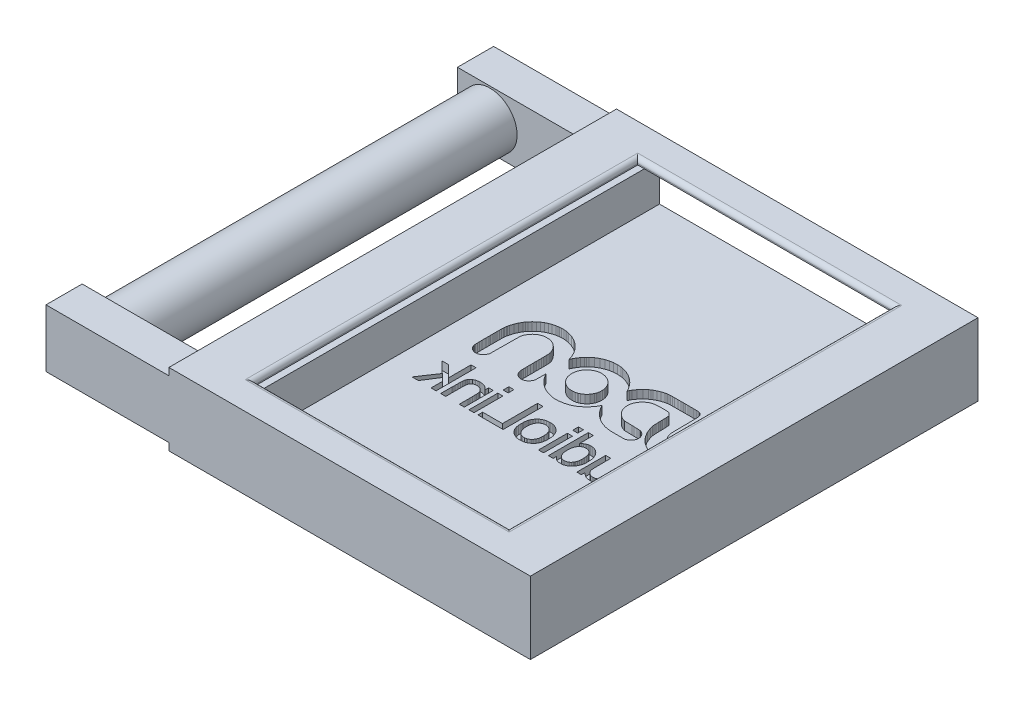
SolidWorks part; units mm, degrees
material "6061 Alloy"
ref_plane "Front" through (0, 0, 0) normal (0, 0, 1) x (1, 0, 0)
ref_plane "Top" through (0, 0, 0) normal (0, 1, 0) x (1, 0, 0)
ref_plane "Right" through (0, 0, 0) normal (1, 0, 0) x (0, 0, -1)
sketch "Sketch1" plane through (0, 0, 0) normal (0, 1, 0) x (1, 0, 0)
  line L1 (-100, -123.825) -> (100, -123.825)
  line L2 (-100, -123.825) -> (-100, 123.825)
  line L3 (-100, 123.825) -> (100, 123.825)
  line L4 (100, -123.825) -> (100, 123.825)
  line L5 (-100, -123.825) -> (100, 123.825) construction
  line L6 (-100, 123.825) -> (100, -123.825) construction
  point P0 (0, 0)
  dimension "D1" = 247.65
  dimension "D2" = 200
extrude "Boss-Extrude1" add sketch "Sketch1" along normal mid plane 40
sketch "Sketch2" plane through (0, 0, 0) normal (0, 1, 0) x (1, 0, 0)
  line L1 (-100, 123.825) -> (-168, 123.825)
  line L2 (-100, 123.825) -> (-100, 103.825)
  line L3 (-100, 103.825) -> (-168, 103.825)
  line L4 (-168, 123.825) -> (-168, 103.825)
  dimension "D1" = 68
  dimension "D2" = 20
extrude "Boss-Extrude2" add sketch "Sketch2" along normal mid plane 32
sketch "Sketch3" plane through (0, 0, 0) normal (0, 0, 1) x (1, 0, 0)
  circle A0 centre (-150, 0) radius 15
  dimension "D1" = 30
  dimension "D2" = 150
extrude "Boss-Extrude3" add sketch "Sketch3" against normal up to surface (103.825 mm away) up to face at (-134, 0, -103.825)
mirror "Mirror1" about plane through (0, 0, 0) normal (0, 0, 1) of "Boss-Extrude2", "Boss-Extrude3"
sketch "Sketch4" plane through (0, 20, 0) normal (0, 1, 0) x (1, 0, 0)
  line L1 (-70.485, -106.045) -> (70.485, -106.045)
  line L2 (-70.485, -106.045) -> (-70.485, 106.045)
  line L3 (-70.485, 106.045) -> (70.485, 106.045)
  line L4 (70.485, -106.045) -> (70.485, 106.045)
  line L5 (-70.485, -106.045) -> (70.485, 106.045) construction
  line L6 (-70.485, 106.045) -> (70.485, -106.045) construction
  point P0 (0, 0)
  dimension "D1" = 212.09
  dimension "D2" = 140.97
extrude "Cut-Extrude1" cut sketch "Sketch4" against normal blind 6.35
sketch "Sketch5" plane through (0, 0, 123.825) normal (0, 0, 1) x (1, 0, 0)
  line L0 (70.485, 13.65) -> (70.485, 20) construction
  line L1 (-89.249, 16.825) -> (89.249, 16.825)
  line L2 (-89.249, 16.825) -> (-89.249, 7.443)
  line L3 (-89.249, 7.443) -> (89.249, 7.443)
  line L4 (89.249, 16.825) -> (89.249, 7.443)
  line L5 (-89.249, 16.825) -> (89.249, 7.443) construction
  line L6 (-89.249, 7.443) -> (89.249, 16.825) construction
  line L7 (-70.485, 13.65) -> (-70.485, 20) construction
  line L8 (70.485, 13.65) -> (70.485, 20) construction
  line L9 (-70.485, 13.65) -> (-70.485, 20) construction
  line L10 (-100, 20) -> (100, 20) construction
  point P0 (0, 12.134)
  dimension "D1" = 9.382
  dimension "D2" = 3.175
  dimension "D3" = 18.764
  dimension "D4" = 18.764
extrude "Cut-Extrude2" cut sketch "Sketch5" along normal offset from surface (246.634 mm away) 16.764 from surface up to face at (0, 16.825, 106.045) offset beyond the face yes starting at face at (-67, 0, -123.825)
fillet "Fillet1" radius 2.54 4 edges at (0, 20, 106.045) (70.485, 20, 0) (-70.485, 20, 0) (0, 20, -106.045)
sketch "Sketch6" plane through (0, 0, -123.825) normal (0, 0, -1) x (-1, 0, 0)
  line L0 (89.249, 7.443) -> (-89.249, 7.443) construction
  line L1 (-76.2, -13.65) -> (76.2, -13.65)
  line L2 (-76.2, -13.65) -> (-76.2, 7.443)
  line L3 (-76.2, 7.443) -> (76.2, 7.443)
  line L4 (76.2, -13.65) -> (76.2, 7.443)
  line L5 (-76.2, -13.65) -> (76.2, 7.443) construction
  line L6 (-76.2, 7.443) -> (76.2, -13.65) construction
  line L7 (-100, -20) -> (100, -20) construction
  point P0 (0, -3.1035)
  dimension "D1" = 152.4
  dimension "D2" = 6.35
extrude "Cut-Extrude3" cut sketch "Sketch6" against normal up to surface (246.634 mm away) up to face at (0, 12.134, 122.809)
sketch "Sketch9" plane through (0, -20, 0) normal (0, -1, 0) x (1, 0, 0)
  line L0 (47.93, -1.8124) -> (48.8593, -2.019)
  line L1 (48.8593, -2.019) -> (50.5205, -2.4998)
  line L2 (50.5205, -2.4998) -> (52.0185, -3.112)
  line L3 (52.0185, -3.112) -> (53.4733, -3.9044)
  line L4 (53.4733, -3.9044) -> (54.222, -4.3835)
  line L5 (54.222, -4.3835) -> (54.8334, -4.8153)
  line L6 (54.8334, -4.8153) -> (56.0096, -5.784)
  line L7 (56.0096, -5.784) -> (57.1117, -6.8762)
  line L8 (57.1117, -6.8762) -> (58.1253, -8.0714)
  line L9 (58.1253, -8.0714) -> (59.0359, -9.3494)
  line L10 (59.0359, -9.3494) -> (59.829, -10.6898)
  line L11 (59.829, -10.6898) -> (60.49, -12.0723)
  line L12 (60.49, -12.0723) -> (61.0045, -13.4765)
  line L13 (61.0045, -13.4765) -> (61.2023, -14.1804)
  line L14 (61.2023, -14.1804) -> (61.4, -15.0085)
  line L15 (61.4, -15.0085) -> (61.6145, -16.1928)
  line L16 (61.6145, -16.1928) -> (61.7109, -17.0783)
  line L17 (61.7109, -17.0783) -> (61.7768, -18.1482)
  line L18 (61.7768, -18.1482) -> (61.8178, -19.4948)
  line L19 (61.8178, -19.4948) -> (61.8396, -21.2101)
  line L20 (61.8396, -21.2101) -> (61.8467, -22.7941)
  line L21 (61.8467, -22.7941) -> (61.8484, -24.0134)
  line L22 (61.8484, -24.0134) -> (61.8486, -24.6763)
  line L23 (61.8486, -24.6763) -> (61.8486, -25.2604)
  line L24 (61.8486, -25.2604) -> (61.8482, -26.327)
  line L25 (61.8482, -26.327) -> (61.846, -27.691)
  line L26 (61.846, -27.691) -> (61.8385, -29.1187)
  line L27 (61.8385, -29.1187) -> (61.8233, -30.1692)
  line L28 (61.8233, -30.1692) -> (61.798, -30.9181)
  line L29 (61.798, -30.9181) -> (61.7599, -31.4412)
  line L30 (61.7599, -31.4412) -> (61.6732, -31.9679)
  line L31 (61.6732, -31.9679) -> (61.5921, -32.2575)
  line L32 (61.5921, -32.2575) -> (61.4441, -32.651)
  line L33 (61.4441, -32.651) -> (61.0089, -33.4052)
  line L34 (61.0089, -33.4052) -> (60.4202, -34.0791)
  line L35 (60.4202, -34.0791) -> (59.7166, -34.6283)
  line L36 (59.7166, -34.6283) -> (59.3337, -34.8425)
  line L37 (59.3337, -34.8425) -> (58.9346, -35.0064)
  line L38 (58.9346, -35.0064) -> (58.0614, -35.1964)
  line L39 (58.0614, -35.1964) -> (57.1488, -35.2022)
  line L40 (57.1488, -35.2022) -> (56.2694, -35.0232)
  line L41 (56.2694, -35.0232) -> (55.8648, -34.8643)
  line L42 (55.8648, -34.8643) -> (55.3692, -34.5995)
  line L43 (55.3692, -34.5995) -> (54.5302, -33.9483)
  line L44 (54.5302, -33.9483) -> (53.8984, -33.1408)
  line L45 (53.8984, -33.1408) -> (53.4792, -32.1837)
  line L46 (53.4792, -32.1837) -> (53.351, -31.6514)
  line L47 (53.351, -31.6514) -> (53.3349, -31.5347)
  line L48 (53.3349, -31.5347) -> (53.3054, -31.1451)
  line L49 (53.3054, -31.1451) -> (53.2796, -30.5535)
  line L50 (53.2796, -30.5535) -> (53.2577, -29.7676)
  line L51 (53.2577, -29.7676) -> (53.2397, -28.795)
  line L52 (53.2397, -28.795) -> (53.2258, -27.6434)
  line L53 (53.2258, -27.6434) -> (53.2161, -26.3204)
  line L54 (53.2161, -26.3204) -> (53.2108, -24.8337)
  line L55 (53.2108, -24.8337) -> (53.2099, -24.0314)
  line L56 (53.2099, -24.0314) -> (53.2069, -22.5476)
  line L57 (53.2069, -22.5476) -> (53.1942, -20.5567)
  line L58 (53.1942, -20.5567) -> (53.1807, -19.4123)
  line L59 (53.1807, -19.4123) -> (53.1636, -18.4351)
  line L60 (53.1636, -18.4351) -> (53.1432, -17.6434)
  line L61 (53.1432, -17.6434) -> (53.1198, -17.055)
  line L62 (53.1198, -17.055) -> (53.0937, -16.6882)
  line L63 (53.0937, -16.6882) -> (53.0797, -16.5934)
  line L64 (53.0797, -16.5934) -> (52.8926, -15.8966)
  line L65 (52.8926, -15.8966) -> (52.3521, -14.5891)
  line L66 (52.3521, -14.5891) -> (51.6095, -13.4123)
  line L67 (51.6095, -13.4123) -> (50.6885, -12.385)
  line L68 (50.6885, -12.385) -> (49.6127, -11.5261)
  line L69 (49.6127, -11.5261) -> (48.4057, -10.8544)
  line L70 (48.4057, -10.8544) -> (47.0912, -10.3889)
  line L71 (47.0912, -10.3889) -> (45.6927, -10.1483)
  line L72 (45.6927, -10.1483) -> (44.9694, -10.1183)
  line L73 (44.9694, -10.1183) -> (43.9951, -10.1684)
  line L74 (43.9951, -10.1684) -> (42.185, -10.5837)
  line L75 (42.185, -10.5837) -> (41.2769, -10.9654)
  line L76 (41.2769, -10.9654) -> (40.8053, -11.229)
  line L77 (40.8053, -11.229) -> (39.795, -11.9878)
  line L78 (39.795, -11.9878) -> (38.8185, -12.936)
  line L79 (38.8185, -12.936) -> (38.0234, -13.93)
  line L80 (38.0234, -13.93) -> (37.7401, -14.3995)
  line L81 (37.7401, -14.3995) -> (37.5607, -14.7386)
  line L82 (37.5607, -14.7386) -> (37.2712, -15.3057)
  line L83 (37.2712, -15.3057) -> (37.0622, -15.844)
  line L84 (37.0622, -15.844) -> (36.9192, -16.4977)
  line L85 (36.9192, -16.4977) -> (36.8279, -17.4103)
  line L86 (36.8279, -17.4103) -> (36.7846, -18.3514)
  line L87 (36.7846, -18.3514) -> (36.7643, -19.1346)
  line L88 (36.7643, -19.1346) -> (36.7489, -20.0635)
  line L89 (36.7489, -20.0635) -> (36.7365, -21.1561)
  line L90 (36.7365, -21.1561) -> (36.7253, -22.4303)
  line L91 (36.7253, -22.4303) -> (36.7135, -23.9041)
  line L92 (36.7135, -23.9041) -> (36.7068, -24.7214)
  line L93 (36.7068, -24.7214) -> (36.7002, -25.5284)
  line L94 (36.7002, -25.5284) -> (36.6881, -26.9863)
  line L95 (36.6881, -26.9863) -> (36.6766, -28.2491)
  line L96 (36.6766, -28.2491) -> (36.664, -29.3326)
  line L97 (36.664, -29.3326) -> (36.6488, -30.2526)
  line L98 (36.6488, -30.2526) -> (36.6297, -31.0248)
  line L99 (36.6297, -31.0248) -> (36.5902, -31.9403)
  line L100 (36.5902, -31.9403) -> (36.5095, -32.7906)
  line L101 (36.5095, -32.7906) -> (36.3858, -33.3329)
  line L102 (36.3858, -33.3329) -> (36.0936, -33.8445)
  line L103 (36.0936, -33.8445) -> (35.8102, -34.1679)
  line L104 (35.8102, -34.1679) -> (35.3632, -34.5848)
  line L105 (35.3632, -34.5848) -> (34.8735, -34.9207)
  line L106 (34.8735, -34.9207) -> (34.6857, -35.0125)
  line L107 (34.6857, -35.0125) -> (34.2701, -35.1085)
  line L108 (34.2701, -35.1085) -> (33.7539, -35.1494)
  line L109 (33.7539, -35.1494) -> (32.9267, -35.1756)
  line L110 (32.9267, -35.1756) -> (32.0403, -35.1876)
  line L111 (32.0403, -35.1876) -> (31.2987, -35.1927)
  line L112 (31.2987, -35.1927) -> (30.4215, -35.196)
  line L113 (30.4215, -35.196) -> (29.3959, -35.1979)
  line L114 (29.3959, -35.1979) -> (28.2091, -35.1987)
  line L115 (28.2091, -35.1987) -> (26.8482, -35.1989)
  line L116 (26.8482, -35.1989) -> (26.0985, -35.1989)
  line L117 (26.0985, -35.1989) -> (25.4237, -35.1989)
  line L118 (25.4237, -35.1989) -> (24.1823, -35.1982)
  line L119 (24.1823, -35.1982) -> (22.573, -35.1954)
  line L120 (22.573, -35.1954) -> (20.8496, -35.1874)
  line L121 (20.8496, -35.1874) -> (19.5398, -35.1726)
  line L122 (19.5398, -35.1726) -> (18.5682, -35.1492)
  line L123 (18.5682, -35.1492) -> (17.8592, -35.1155)
  line L124 (17.8592, -35.1155) -> (17.1232, -35.0417)
  line L125 (17.1232, -35.0417) -> (16.7409, -34.9742)
  line L126 (16.7409, -34.9742) -> (15.8881, -34.7797)
  line L127 (15.8881, -34.7797) -> (14.2327, -34.2776)
  line L128 (14.2327, -34.2776) -> (12.6521, -33.628)
  line L129 (12.6521, -33.628) -> (11.1562, -32.8348)
  line L130 (11.1562, -32.8348) -> (10.443, -32.3856)
  line L131 (10.443, -32.3856) -> (9.6232, -31.7926)
  line L132 (9.6232, -31.7926) -> (8.0064, -30.3585)
  line L133 (8.0064, -30.3585) -> (6.5288, -28.7146)
  line L134 (6.5288, -28.7146) -> (5.3208, -27.006)
  line L135 (5.3208, -27.006) -> (4.8587, -26.1729)
  line L136 (4.8587, -26.1729) -> (4.4117, -25.2748)
  line L137 (4.4117, -25.2748) -> (3.998, -26.0686)
  line L138 (3.998, -26.0686) -> (3.5333, -26.9017)
  line L139 (3.5333, -26.9017) -> (2.4731, -28.475)
  line L140 (2.4731, -28.475) -> (1.2523, -29.914)
  line L141 (1.2523, -29.914) -> (-0.1132, -31.2064)
  line L142 (-0.1132, -31.2064) -> (-1.607, -32.34)
  line L143 (-1.607, -32.34) -> (-3.2132, -33.3026)
  line L144 (-3.2132, -33.3026) -> (-4.9154, -34.0818)
  line L145 (-4.9154, -34.0818) -> (-6.6976, -34.6655)
  line L146 (-6.6976, -34.6655) -> (-7.6137, -34.8801)
  line L147 (-7.6137, -34.8801) -> (-8.6686, -35.0616)
  line L148 (-8.6686, -35.0616) -> (-10.7713, -35.2252)
  line L149 (-10.7713, -35.2252) -> (-12.8491, -35.1279)
  line L150 (-12.8491, -35.1279) -> (-14.8833, -34.7755)
  line L151 (-14.8833, -34.7755) -> (-16.8553, -34.1736)
  line L152 (-16.8553, -34.1736) -> (-18.7463, -33.3279)
  line L153 (-18.7463, -33.3279) -> (-20.5378, -32.2442)
  line L154 (-20.5378, -32.2442) -> (-22.2109, -30.9281)
  line L155 (-22.2109, -30.9281) -> (-22.9973, -30.1847)
  line L156 (-22.9973, -30.1847) -> (-23.5248, -29.6247)
  line L157 (-23.5248, -29.6247) -> (-24.5397, -28.3737)
  line L158 (-24.5397, -28.3737) -> (-25.4499, -27.0237)
  line L159 (-25.4499, -27.0237) -> (-26.1944, -25.6654)
  line L160 (-26.1944, -25.6654) -> (-26.4854, -25.0115)
  line L161 (-26.4854, -25.0115) -> (-26.7632, -24.328)
  line L162 (-26.7632, -24.328) -> (-27.0924, -25.382)
  line L163 (-27.0924, -25.382) -> (-27.4778, -26.465)
  line L164 (-27.4778, -26.465) -> (-28.506, -28.5948)
  line L165 (-28.506, -28.5948) -> (-29.8176, -30.5858)
  line L166 (-29.8176, -30.5858) -> (-31.3414, -32.3296)
  line L167 (-31.3414, -32.3296) -> (-32.1605, -33.075)
  line L168 (-32.1605, -33.075) -> (-33.1539, -33.8619)
  line L169 (-33.1539, -33.8619) -> (-35.1274, -35.1509)
  line L170 (-35.1274, -35.1509) -> (-37.1834, -36.1065)
  line L171 (-37.1834, -36.1065) -> (-39.442, -36.7846)
  line L172 (-39.442, -36.7846) -> (-40.6848, -37.0371)
  line L173 (-40.6848, -37.0371) -> (-41.3523, -37.1437)
  line L174 (-41.3523, -37.1437) -> (-42.5862, -37.2657)
  line L175 (-42.5862, -37.2657) -> (-43.7685, -37.2661)
  line L176 (-43.7685, -37.2661) -> (-44.9993, -37.1451)
  line L177 (-44.9993, -37.1451) -> (-45.6641, -37.0391)
  line L178 (-45.6641, -37.0391) -> (-46.5297, -36.868)
  line L179 (-46.5297, -36.868) -> (-48.1852, -36.4278)
  line L180 (-48.1852, -36.4278) -> (-49.7428, -35.8549)
  line L181 (-49.7428, -35.8549) -> (-51.2063, -35.1471)
  line L182 (-51.2063, -35.1471) -> (-52.5794, -34.302)
  line L183 (-52.5794, -34.302) -> (-53.8658, -33.3174)
  line L184 (-53.8658, -33.3174) -> (-55.0694, -32.1909)
  line L185 (-55.0694, -32.1909) -> (-56.1937, -30.9202)
  line L186 (-56.1937, -30.9202) -> (-56.7274, -30.2301)
  line L187 (-56.7274, -30.2301) -> (-57.2616, -29.4642)
  line L188 (-57.2616, -29.4642) -> (-58.1905, -27.8525)
  line L189 (-58.1905, -27.8525) -> (-58.9425, -26.1127)
  line L190 (-58.9425, -26.1127) -> (-59.5287, -24.2193)
  line L191 (-59.5287, -24.2193) -> (-59.7631, -23.2069)
  line L192 (-59.7631, -23.2069) -> (-59.8639, -22.7055)
  line L193 (-59.8639, -22.7055) -> (-59.9693, -21.9562)
  line L194 (-59.9693, -21.9562) -> (-60.0143, -21.2913)
  line L195 (-60.0143, -21.2913) -> (-60.0433, -20.3602)
  line L196 (-60.0433, -20.3602) -> (-60.0598, -19.0481)
  line L197 (-60.0598, -19.0481) -> (-60.0662, -17.7451)
  line L198 (-60.0662, -17.7451) -> (-60.0684, -16.6976)
  line L199 (-60.0684, -16.6976) -> (-60.0695, -15.4904)
  line L200 (-60.0695, -15.4904) -> (-60.0699, -14.109)
  line L201 (-60.0699, -14.109) -> (-60.07, -13.3486)
  line L202 (-60.07, -13.3486) -> (-60.0679, -11.6508)
  line L203 (-60.0679, -11.6508) -> (-60.057, -9.3283)
  line L204 (-60.057, -9.3283) -> (-60.0452, -7.9785)
  line L205 (-60.0452, -7.9785) -> (-60.0302, -6.8266)
  line L206 (-60.0302, -6.8266) -> (-60.0125, -5.9063)
  line L207 (-60.0125, -5.9063) -> (-59.9926, -5.2512)
  line L208 (-59.9926, -5.2512) -> (-59.9708, -4.8951)
  line L209 (-59.9708, -4.8951) -> (-59.9593, -4.8396)
  line L210 (-59.9593, -4.8396) -> (-59.9043, -4.756)
  line L211 (-59.9043, -4.756) -> (-59.7656, -4.4437)
  line L212 (-59.7656, -4.4437) -> (-59.699, -4.2534)
  line L213 (-59.699, -4.2534) -> (-59.6021, -4.0237)
  line L214 (-59.6021, -4.0237) -> (-59.2623, -3.4944)
  line L215 (-59.2623, -3.4944) -> (-58.5336, -2.6951)
  line L216 (-58.5336, -2.6951) -> (-58.0151, -2.2908)
  line L217 (-58.0151, -2.2908) -> (-57.7273, -2.1311)
  line L218 (-57.7273, -2.1311) -> (-57.055, -1.8689)
  line L219 (-57.055, -1.8689) -> (-56.3263, -1.7002)
  line L220 (-56.3263, -1.7002) -> (-55.6278, -1.6448)
  line L221 (-55.6278, -1.6448) -> (-55.3171, -1.666)
  line L222 (-55.3171, -1.666) -> (-54.7785, -1.7767)
  line L223 (-54.7785, -1.7767) -> (-53.7585, -2.2139)
  line L224 (-53.7585, -2.2139) -> (-52.8596, -2.9046)
  line L225 (-52.8596, -2.9046) -> (-52.136, -3.807)
  line L226 (-52.136, -3.807) -> (-51.8568, -4.3246)
  line L227 (-51.8568, -4.3246) -> (-51.4985, -5.0999)
  line L228 (-51.4985, -5.0999) -> (-51.4312, -13.6724)
  line L229 (-51.4312, -13.6724) -> (-51.4252, -14.4369)
  line L230 (-51.4252, -14.4369) -> (-51.4139, -15.8277)
  line L231 (-51.4139, -15.8277) -> (-51.4034, -17.0448)
  line L232 (-51.4034, -17.0448) -> (-51.393, -18.101)
  line L233 (-51.393, -18.101) -> (-51.3824, -19.0094)
  line L234 (-51.3824, -19.0094) -> (-51.371, -19.7826)
  line L235 (-51.371, -19.7826) -> (-51.3516, -20.7173)
  line L236 (-51.3516, -20.7173) -> (-51.3186, -21.6106)
  line L237 (-51.3186, -21.6106) -> (-51.2741, -22.1949)
  line L238 (-51.2741, -22.1949) -> (-51.1775, -22.7169)
  line L239 (-51.1775, -22.7169) -> (-51.0877, -22.9784)
  line L240 (-51.0877, -22.9784) -> (-50.776, -23.7156)
  line L241 (-50.776, -23.7156) -> (-49.9983, -25.0764)
  line L242 (-49.9983, -25.0764) -> (-49.0459, -26.2477)
  line L243 (-49.0459, -26.2477) -> (-47.9559, -27.1837)
  line L244 (-47.9559, -27.1837) -> (-47.371, -27.5492)
  line L245 (-47.371, -27.5492) -> (-46.8306, -27.8335)
  line L246 (-46.8306, -27.8335) -> (-45.853, -28.2463)
  line L247 (-45.853, -28.2463) -> (-44.8852, -28.4825)
  line L248 (-44.8852, -28.4825) -> (-43.7739, -28.5794)
  line L249 (-43.7739, -28.5794) -> (-43.1165, -28.5874)
  line L250 (-43.1165, -28.5874) -> (-42.6016, -28.5831)
  line L251 (-42.6016, -28.5831) -> (-41.8473, -28.5534)
  line L252 (-41.8473, -28.5534) -> (-41.2968, -28.4714)
  line L253 (-41.2968, -28.4714) -> (-40.7543, -28.3077)
  line L254 (-40.7543, -28.3077) -> (-40.4247, -28.186)
  line L255 (-40.4247, -28.186) -> (-39.9657, -27.9967)
  line L256 (-39.9657, -27.9967) -> (-39.0406, -27.5409)
  line L257 (-39.0406, -27.5409) -> (-38.6885, -27.3306)
  line L258 (-38.6885, -27.3306) -> (-38.2703, -27.0276)
  line L259 (-38.2703, -27.0276) -> (-37.4493, -26.2898)
  line L260 (-37.4493, -26.2898) -> (-36.6972, -25.4315)
  line L261 (-36.6972, -25.4315) -> (-36.0723, -24.5191)
  line L262 (-36.0723, -24.5191) -> (-35.8257, -24.0634)
  line L263 (-35.8257, -24.0634) -> (-35.5228, -23.4356)
  line L264 (-35.5228, -23.4356) -> (-35.2091, -22.5816)
  line L265 (-35.2091, -22.5816) -> (-35.0772, -21.8826)
  line L266 (-35.0772, -21.8826) -> (-34.9942, -20.9297)
  line L267 (-34.9942, -20.9297) -> (-34.9571, -19.9706)
  line L268 (-34.9571, -19.9706) -> (-34.9417, -19.1848)
  line L269 (-34.9417, -19.1848) -> (-34.9322, -18.2629)
  line L270 (-34.9322, -18.2629) -> (-34.9272, -17.1889)
  line L271 (-34.9272, -17.1889) -> (-34.9253, -15.9467)
  line L272 (-34.9253, -15.9467) -> (-34.925, -14.52)
  line L273 (-34.925, -14.52) -> (-34.925, -13.7326)
  line L274 (-34.925, -13.7326) -> (-34.9244, -12.8119)
  line L275 (-34.9244, -12.8119) -> (-34.9199, -11.1176)
  line L276 (-34.9199, -11.1176) -> (-34.911, -9.6236)
  line L277 (-34.911, -9.6236) -> (-34.8978, -8.335)
  line L278 (-34.8978, -8.335) -> (-34.8803, -7.2571)
  line L279 (-34.8803, -7.2571) -> (-34.8587, -6.3951)
  line L280 (-34.8587, -6.3951) -> (-34.833, -5.7541)
  line L281 (-34.833, -5.7541) -> (-34.8033, -5.3394)
  line L282 (-34.8033, -5.3394) -> (-34.787, -5.2185)
  line L283 (-34.787, -5.2185) -> (-34.6999, -4.8323)
  line L284 (-34.6999, -4.8323) -> (-34.4399, -4.1124)
  line L285 (-34.4399, -4.1124) -> (-34.0739, -3.4695)
  line L286 (-34.0739, -3.4695) -> (-33.6116, -2.9118)
  line L287 (-33.6116, -2.9118) -> (-33.063, -2.4477)
  line L288 (-33.063, -2.4477) -> (-32.4378, -2.0856)
  line L289 (-32.4378, -2.0856) -> (-31.746, -1.8338)
  line L290 (-31.746, -1.8338) -> (-30.9973, -1.7005)
  line L291 (-30.9973, -1.7005) -> (-30.6047, -1.681)
  line L292 (-30.6047, -1.681) -> (-29.981, -1.7185)
  line L293 (-29.981, -1.7185) -> (-28.8386, -2.046)
  line L294 (-28.8386, -2.046) -> (-27.851, -2.7004)
  line L295 (-27.851, -2.7004) -> (-27.0358, -3.6702)
  line L296 (-27.0358, -3.6702) -> (-26.6984, -4.2697)
  line L297 (-26.6984, -4.2697) -> (-26.585, -4.5073)
  line L298 (-26.585, -4.5073) -> (-26.4362, -4.9681)
  line L299 (-26.4362, -4.9681) -> (-26.3751, -5.4722)
  line L300 (-26.3751, -5.4722) -> (-26.3502, -5.9652)
  line L301 (-26.3502, -5.9652) -> (-26.3328, -6.6345)
  line L302 (-26.3328, -6.6345) -> (-26.3184, -7.5234)
  line L303 (-26.3184, -7.5234) -> (-26.3109, -8.0637)
  line L304 (-26.3109, -8.0637) -> (-26.2689, -11.1546)
  line L305 (-26.2689, -11.1546) -> (-25.7104, -10.1744)
  line L306 (-25.7104, -10.1744) -> (-25.2365, -9.3917)
  line L307 (-25.2365, -9.3917) -> (-24.177, -7.917)
  line L308 (-24.177, -7.917) -> (-22.9796, -6.5718)
  line L309 (-22.9796, -6.5718) -> (-21.6581, -5.3662)
  line L310 (-21.6581, -5.3662) -> (-20.2262, -4.3101)
  line L311 (-20.2262, -4.3101) -> (-18.6974, -3.4138)
  line L312 (-18.6974, -3.4138) -> (-17.0854, -2.6873)
  line L313 (-17.0854, -2.6873) -> (-15.404, -2.1406)
  line L314 (-15.404, -2.1406) -> (-14.5415, -1.9379)
  line L315 (-14.5415, -1.9379) -> (-14.0986, -1.847)
  line L316 (-14.0986, -1.847) -> (-13.2307, -1.6695)
  line L317 (-13.2307, -1.6695) -> (-12.9126, -1.6047)
  line L318 (-12.9126, -1.6047) -> (-12.466, -1.5337)
  line L319 (-12.466, -1.5337) -> (-11.4389, -1.475)
  line L320 (-11.4389, -1.475) -> (-9.655, -1.5789)
  line L321 (-9.655, -1.5789) -> (-7.0806, -2.0304)
  line L322 (-7.0806, -2.0304) -> (-5.2179, -2.5662)
  line L323 (-5.2179, -2.5662) -> (-4.1006, -3.001)
  line L324 (-4.1006, -3.001) -> (-3.5977, -3.2385)
  line L325 (-3.5977, -3.2385) -> (-2.4454, -3.8854)
  line L326 (-2.4454, -3.8854) -> (-0.2515, -5.484)
  line L327 (-0.2515, -5.484) -> (1.7045, -7.4005)
  line L328 (1.7045, -7.4005) -> (3.3142, -9.5288)
  line L329 (3.3142, -9.5288) -> (3.9552, -10.6392)
  line L330 (3.9552, -10.6392) -> (4.3904, -11.4794)
  line L331 (4.3904, -11.4794) -> (4.9413, -10.4279)
  line L332 (4.9413, -10.4279) -> (5.3263, -9.7401)
  line L333 (5.3263, -9.7401) -> (6.2161, -8.4126)
  line L334 (6.2161, -8.4126) -> (7.2502, -7.1614)
  line L335 (7.2502, -7.1614) -> (8.4106, -6.0016)
  line L336 (8.4106, -6.0016) -> (9.6792, -4.9484)
  line L337 (9.6792, -4.9484) -> (11.0377, -4.0168)
  line L338 (11.0377, -4.0168) -> (12.468, -3.2219)
  line L339 (12.468, -3.2219) -> (13.9519, -2.5787)
  line L340 (13.9519, -2.5787) -> (14.7084, -2.3187)
  line L341 (14.7084, -2.3187) -> (15.5331, -2.0749)
  line L342 (15.5331, -2.0749) -> (17.1024, -1.7339)
  line L343 (17.1024, -1.7339) -> (18.4035, -1.5869)
  line L344 (18.4035, -1.5869) -> (19.4225, -1.5316)
  line L345 (19.4225, -1.5316) -> (20.6203, -1.5047)
  line L346 (20.6203, -1.5047) -> (22.0461, -1.5013)
  line L347 (22.0461, -1.5013) -> (22.86, -1.5068)
  line L348 (22.86, -1.5068) -> (26.9875, -1.5439)
  line L349 (26.9875, -1.5439) -> (27.7793, -1.9096)
  line L350 (27.7793, -1.9096) -> (28.2315, -2.1493)
  line L351 (28.2315, -2.1493) -> (29.0123, -2.7454)
  line L352 (29.0123, -2.7454) -> (29.621, -3.4699)
  line L353 (29.621, -3.4699) -> (30.0487, -4.2897)
  line L354 (30.0487, -4.2897) -> (30.2865, -5.172)
  line L355 (30.2865, -5.172) -> (30.3255, -6.0836)
  line L356 (30.3255, -6.0836) -> (30.1568, -6.9916)
  line L357 (30.1568, -6.9916) -> (29.7716, -7.8632)
  line L358 (29.7716, -7.8632) -> (29.495, -8.2749)
  line L359 (29.495, -8.2749) -> (29.0358, -8.7861)
  line L360 (29.0358, -8.7861) -> (27.8992, -9.6272)
  line L361 (27.8992, -9.6272) -> (27.3275, -9.8789)
  line L362 (27.3275, -9.8789) -> (27.2543, -9.8968)
  line L363 (27.2543, -9.8968) -> (27.0073, -9.9317)
  line L364 (27.0073, -9.9317) -> (26.3933, -9.981)
  line L365 (26.3933, -9.981) -> (25.1434, -10.0404)
  line L366 (25.1434, -10.0404) -> (23.4327, -10.0907)
  line L367 (23.4327, -10.0907) -> (22.4155, -10.1121)
  line L368 (22.4155, -10.1121) -> (17.9705, -10.1949)
  line L369 (17.9705, -10.1949) -> (17.0207, -10.5531)
  line L370 (17.0207, -10.5531) -> (16.3324, -10.846)
  line L371 (16.3324, -10.846) -> (15.0675, -11.5821)
  line L372 (15.0675, -11.5821) -> (13.9649, -12.4963)
  line L373 (13.9649, -12.4963) -> (13.0414, -13.5613)
  line L374 (13.0414, -13.5613) -> (12.3136, -14.7502)
  line L375 (12.3136, -14.7502) -> (11.7978, -16.0359)
  line L376 (11.7978, -16.0359) -> (11.5108, -17.3913)
  line L377 (11.5108, -17.3913) -> (11.4692, -18.7893)
  line L378 (11.4692, -18.7893) -> (11.5455, -19.4959)
  line L379 (11.5455, -19.4959) -> (11.6767, -20.1945)
  line L380 (11.6767, -20.1945) -> (12.0623, -21.4564)
  line L381 (12.0623, -21.4564) -> (12.6362, -22.5846)
  line L382 (12.6362, -22.5846) -> (13.4271, -23.6357)
  line L383 (13.4271, -23.6357) -> (13.9129, -24.1499)
  line L384 (13.9129, -24.1499) -> (14.2939, -24.5126)
  line L385 (14.2939, -24.5126) -> (15.0462, -25.1282)
  line L386 (15.0462, -25.1282) -> (16.2354, -25.8314)
  line L387 (16.2354, -25.8314) -> (17.1352, -26.1956)
  line L388 (17.1352, -26.1956) -> (17.6372, -26.3521)
  line L389 (17.6372, -26.3521) -> (18.7495, -26.5798)
  line L390 (18.7495, -26.5798) -> (20.1313, -26.7051)
  line L391 (20.1313, -26.7051) -> (21.4348, -26.7401)
  line L392 (21.4348, -26.7401) -> (22.4663, -26.7384)
  line L393 (22.4663, -26.7384) -> (23.0378, -26.7308)
  line L394 (23.0378, -26.7308) -> (23.5826, -26.7212)
  line L395 (23.5826, -26.7212) -> (24.4877, -26.6984)
  line L396 (24.4877, -26.6984) -> (25.1826, -26.6629)
  line L397 (25.1826, -26.6629) -> (25.7101, -26.6053)
  line L398 (25.7101, -26.6053) -> (26.2808, -26.4567)
  line L399 (26.2808, -26.4567) -> (26.8544, -26.0928)
  line L400 (26.8544, -26.0928) -> (27.1571, -25.8185)
  line L401 (27.1571, -25.8185) -> (27.4357, -25.5494)
  line L402 (27.4357, -25.5494) -> (27.7976, -24.9893)
  line L403 (27.7976, -24.9893) -> (27.9422, -24.292)
  line L404 (27.9422, -24.292) -> (27.9993, -23.5723)
  line L405 (27.9993, -23.5723) -> (28.0381, -22.5723)
  line L406 (28.0381, -22.5723) -> (28.0698, -21.2265)
  line L407 (28.0698, -21.2265) -> (28.0865, -20.4034)
  line L408 (28.0865, -20.4034) -> (28.0982, -19.8547)
  line L409 (28.0982, -19.8547) -> (28.1231, -18.861)
  line L410 (28.1231, -18.861) -> (28.1652, -17.6148)
  line L411 (28.1652, -17.6148) -> (28.2323, -16.3682)
  line L412 (28.2323, -16.3682) -> (28.3151, -15.5383)
  line L413 (28.3151, -15.5383) -> (28.3635, -15.2599)
  line L414 (28.3635, -15.2599) -> (28.7437, -13.783)
  line L415 (28.7437, -13.783) -> (29.837, -11.001)
  line L416 (29.837, -11.001) -> (31.3485, -8.4905)
  line L417 (31.3485, -8.4905) -> (32.7383, -6.8163)
  line L418 (32.7383, -6.8163) -> (33.7796, -5.8114)
  line L419 (33.7796, -5.8114) -> (34.3332, -5.3448)
  line L420 (34.3332, -5.3448) -> (35.1932, -4.6885)
  line L421 (35.1932, -4.6885) -> (36.9311, -3.5871)
  line L422 (36.9311, -3.5871) -> (38.7596, -2.7366)
  line L423 (38.7596, -2.7366) -> (40.7584, -2.0999)
  line L424 (40.7584, -2.0999) -> (41.8465, -1.85)
  line L425 (41.8465, -1.85) -> (42.6782, -1.6958)
  line L426 (42.6782, -1.6958) -> (44.211, -1.5159)
  line L427 (44.211, -1.5159) -> (45.6624, -1.507)
  line L428 (45.6624, -1.507) -> (47.1435, -1.6682)
  line L429 (47.1435, -1.6682) -> (47.93, -1.8124)
  line L430 (22.479, 27.6239) -> (22.8987, 27.475)
  line L431 (22.8987, 27.475) -> (23.6208, 27.1527)
  line L432 (23.6208, 27.1527) -> (24.2551, 26.7544)
  line L433 (24.2551, 26.7544) -> (24.884, 26.2286)
  line L434 (24.884, 26.2286) -> (25.2222, 25.9016)
  line L435 (25.2222, 25.9016) -> (25.5751, 25.5248)
  line L436 (25.5751, 25.5248) -> (26.1896, 24.7175)
  line L437 (26.1896, 24.7175) -> (26.6918, 23.8219)
  line L438 (26.6918, 23.8219) -> (27.0931, 22.8177)
  line L439 (27.0931, 22.8177) -> (27.2595, 22.2686)
  line L440 (27.2595, 22.2686) -> (27.3162, 22.0251)
  line L441 (27.3162, 22.0251) -> (27.407, 21.4175)
  line L442 (27.407, 21.4175) -> (27.4863, 20.2929)
  line L443 (27.4863, 20.2929) -> (27.4858, 18.6436)
  line L444 (27.4858, 18.6436) -> (27.4058, 17.5012)
  line L445 (27.4058, 17.5012) -> (27.3146, 16.8732)
  line L446 (27.3146, 16.8732) -> (27.2577, 16.6171)
  line L447 (27.2577, 16.6171) -> (27.0032, 15.7815)
  line L448 (27.0032, 15.7815) -> (26.3203, 14.2855)
  line L449 (26.3203, 14.2855) -> (25.4256, 13.0509)
  line L450 (25.4256, 13.0509) -> (24.3438, 12.1115)
  line L451 (24.3438, 12.1115) -> (23.7403, 11.7631)
  line L452 (23.7403, 11.7631) -> (23.3338, 11.5756)
  line L453 (23.3338, 11.5756) -> (22.5586, 11.3014)
  line L454 (22.5586, 11.3014) -> (21.7685, 11.1489)
  line L455 (21.7685, 11.1489) -> (20.8854, 11.1028)
  line L456 (20.8854, 11.1028) -> (20.3844, 11.115)
  line L457 (20.3844, 11.115) -> (20.0415, 11.1329)
  line L458 (20.0415, 11.1329) -> (19.5012, 11.1873)
  line L459 (19.5012, 11.1873) -> (18.8608, 11.3595)
  line L460 (18.8608, 11.3595) -> (18.396, 11.5692)
  line L461 (18.396, 11.5692) -> (17.6424, 12.0268)
  line L462 (17.6424, 12.0268) -> (16.9802, 12.5609)
  line L463 (16.9802, 12.5609) -> (16.383, 13.1497)
  line L464 (16.383, 13.1497) -> (16.383, 9.2636)
  line L465 (16.383, 9.2636) -> (16.383, 5.3776)
  line L466 (16.383, 5.3776) -> (14.986, 5.3776)
  line L467 (14.986, 5.3776) -> (13.589, 5.3776)
  line L468 (13.589, 5.3776) -> (13.589, 16.4266)
  line L469 (13.589, 16.4266) -> (13.589, 27.4756)
  line L470 (13.589, 27.4756) -> (14.9225, 27.4756)
  line L471 (14.9225, 27.4756) -> (16.256, 27.4756)
  line L472 (16.256, 27.4756) -> (16.256, 26.592)
  line L473 (16.256, 26.592) -> (16.256, 25.7085)
  line L474 (16.256, 25.7085) -> (16.8459, 26.3391)
  line L475 (16.8459, 26.3391) -> (17.1471, 26.6263)
  line L476 (17.1471, 26.6263) -> (17.8866, 27.1671)
  line L477 (17.8866, 27.1671) -> (18.2698, 27.3803)
  line L478 (18.2698, 27.3803) -> (18.7579, 27.6029)
  line L479 (18.7579, 27.6029) -> (19.4199, 27.7687)
  line L480 (19.4199, 27.7687) -> (20.0305, 27.8114)
  line L481 (20.0305, 27.8114) -> (20.4421, 27.8237)
  line L482 (20.4421, 27.8237) -> (20.8023, 27.8296)
  line L483 (20.8023, 27.8296) -> (21.3963, 27.8185)
  line L484 (21.3963, 27.8185) -> (22.0791, 27.7338)
  line L485 (22.0791, 27.7338) -> (22.479, 27.6239)
  line L486 (0.2993, 27.6553) -> (1.0056, 27.441)
  line L487 (1.0056, 27.441) -> (2.3336, 26.7855)
  line L488 (2.3336, 26.7855) -> (3.4968, 25.8685)
  line L489 (3.4968, 25.8685) -> (4.4331, 24.7391)
  line L490 (4.4331, 24.7391) -> (4.7966, 24.1101)
  line L491 (4.7966, 24.1101) -> (5.0057, 23.6647)
  line L492 (5.0057, 23.6647) -> (5.3258, 22.7767)
  line L493 (5.3258, 22.7767) -> (5.5336, 21.806)
  line L494 (5.5336, 21.806) -> (5.6512, 20.6494)
  line L495 (5.6512, 20.6494) -> (5.683, 19.9691)
  line L496 (5.683, 19.9691) -> (5.6979, 19.1586)
  line L497 (5.6979, 19.1586) -> (5.6354, 17.7727)
  line L498 (5.6354, 17.7727) -> (5.4312, 16.5926)
  line L499 (5.4312, 16.5926) -> (5.0632, 15.4892)
  line L500 (5.0632, 15.4892) -> (4.8107, 14.9259)
  line L501 (4.8107, 14.9259) -> (4.5421, 14.4178)
  line L502 (4.5421, 14.4178) -> (3.9128, 13.5164)
  line L503 (3.9128, 13.5164) -> (3.1506, 12.7581)
  line L504 (3.1506, 12.7581) -> (2.2435, 12.1308)
  line L505 (2.2435, 12.1308) -> (1.7317, 11.8626)
  line L506 (1.7317, 11.8626) -> (1.2778, 11.656)
  line L507 (1.2778, 11.656) -> (0.4519, 11.3533)
  line L508 (0.4519, 11.3533) -> (-0.3621, 11.1771)
  line L509 (-0.3621, 11.1771) -> (-1.2809, 11.102)
  line L510 (-1.2809, 11.102) -> (-1.816, 11.0944)
  line L511 (-1.816, 11.0944) -> (-2.4479, 11.1159)
  line L512 (-2.4479, 11.1159) -> (-3.6445, 11.2798)
  line L513 (-3.6445, 11.2798) -> (-4.7465, 11.6015)
  line L514 (-4.7465, 11.6015) -> (-5.7479, 12.0769)
  line L515 (-5.7479, 12.0769) -> (-6.6427, 12.7016)
  line L516 (-6.6427, 12.7016) -> (-7.4249, 13.4715)
  line L517 (-7.4249, 13.4715) -> (-8.0885, 14.3824)
  line L518 (-8.0885, 14.3824) -> (-8.6273, 15.4301)
  line L519 (-8.6273, 15.4301) -> (-8.8481, 16.0039)
  line L520 (-8.8481, 16.0039) -> (-9.0313, 16.5932)
  line L521 (-9.0313, 16.5932) -> (-9.1787, 17.5052)
  line L522 (-9.1787, 17.5052) -> (-9.2267, 18.3941)
  line L523 (-9.2267, 18.3941) -> (-9.2446, 18.9903)
  line L524 (-9.2446, 18.9903) -> (-9.2554, 19.8309)
  line L525 (-9.2554, 19.8309) -> (-9.1924, 21.2543)
  line L526 (-9.1924, 21.2543) -> (-9.0002, 22.4368)
  line L527 (-9.0002, 22.4368) -> (-8.6586, 23.5017)
  line L528 (-8.6586, 23.5017) -> (-8.4256, 24.0285)
  line L529 (-8.4256, 24.0285) -> (-8.0707, 24.6639)
  line L530 (-8.0707, 24.6639) -> (-7.1311, 25.8054)
  line L531 (-7.1311, 25.8054) -> (-5.9292, 26.7403)
  line L532 (-5.9292, 26.7403) -> (-4.5186, 27.4269)
  line L533 (-4.5186, 27.4269) -> (-3.7516, 27.6642)
  line L534 (-3.7516, 27.6642) -> (-3.3479, 27.7427)
  line L535 (-3.3479, 27.7427) -> (-2.321, 27.8312)
  line L536 (-2.321, 27.8312) -> (-1.1768, 27.8287)
  line L537 (-1.1768, 27.8287) -> (-0.1256, 27.7357)
  line L538 (-0.1256, 27.7357) -> (0.2993, 27.6553)
  line L539 (63.5569, 26.3643) -> (63.4932, 26.1997)
  line L540 (63.4932, 26.1997) -> (63.2571, 25.5875)
  line L541 (63.2571, 25.5875) -> (62.8908, 24.6356)
  line L542 (62.8908, 24.6356) -> (62.4116, 23.3892)
  line L543 (62.4116, 23.3892) -> (61.8368, 21.8934)
  line L544 (61.8368, 21.8934) -> (61.1838, 20.1935)
  line L545 (61.1838, 20.1935) -> (60.0957, 17.3597)
  line L546 (60.0957, 17.3597) -> (59.3232, 15.3471)
  line L547 (59.3232, 15.3471) -> (55.5217, 5.4411)
  line L548 (55.5217, 5.4411) -> (53.8743, 5.4057)
  line L549 (53.8743, 5.4057) -> (53.4453, 5.3985)
  line L550 (53.4453, 5.3985) -> (52.7982, 5.4018)
  line L551 (52.7982, 5.4018) -> (52.3968, 5.4316)
  line L552 (52.3968, 5.4316) -> (52.198, 5.491)
  line L553 (52.198, 5.491) -> (52.1612, 5.5327)
  line L554 (52.1612, 5.5327) -> (52.1124, 5.6527)
  line L555 (52.1124, 5.6527) -> (51.8841, 6.2124)
  line L556 (51.8841, 6.2124) -> (51.5015, 7.1497)
  line L557 (51.5015, 7.1497) -> (50.9886, 8.4057)
  line L558 (50.9886, 8.4057) -> (50.3694, 9.9219)
  line L559 (50.3694, 9.9219) -> (49.6678, 11.6395)
  line L560 (49.6678, 11.6395) -> (48.5134, 14.4652)
  line L561 (48.5134, 14.4652) -> (46.91, 18.3897)
  line L562 (46.91, 18.3897) -> (45.7641, 21.1941)
  line L563 (45.7641, 21.1941) -> (45.0721, 22.8873)
  line L564 (45.0721, 22.8873) -> (44.4657, 24.371)
  line L565 (44.4657, 24.371) -> (43.9688, 25.5865)
  line L566 (43.9688, 25.5865) -> (43.6054, 26.475)
  line L567 (43.6054, 26.475) -> (43.3995, 26.9779)
  line L568 (43.3995, 26.9779) -> (43.3632, 27.0664)
  line L569 (43.3632, 27.0664) -> (43.19, 27.4827)
  line L570 (43.19, 27.4827) -> (44.9249, 27.4474)
  line L571 (44.9249, 27.4474) -> (46.6599, 27.4121)
  line L572 (46.6599, 27.4121) -> (47.9301, 24.0768)
  line L573 (47.9301, 24.0768) -> (49.2004, 20.7415)
  line L574 (49.2004, 20.7415) -> (53.7784, 20.7748)
  line L575 (53.7784, 20.7748) -> (58.3565, 20.8081)
  line L576 (58.3565, 20.8081) -> (59.563, 24.1414)
  line L577 (59.563, 24.1414) -> (60.7695, 27.4747)
  line L578 (60.7695, 27.4747) -> (62.3793, 27.4752)
  line L579 (62.3793, 27.4752) -> (63.9891, 27.4756)
  line L580 (63.9891, 27.4756) -> (63.5569, 26.3643)
  line L581 (-48.514, 16.4266) -> (-48.514, 5.3776)
  line L582 (-48.514, 5.3776) -> (-49.911, 5.3776)
  line L583 (-49.911, 5.3776) -> (-51.308, 5.3776)
  line L584 (-51.308, 5.3776) -> (-51.308, 11.6192)
  line L585 (-51.308, 11.6192) -> (-51.308, 17.8608)
  line L586 (-51.308, 17.8608) -> (-54.4314, 14.6672)
  line L587 (-54.4314, 14.6672) -> (-57.5549, 11.4736)
  line L588 (-57.5549, 11.4736) -> (-59.4162, 11.4765)
  line L589 (-59.4162, 11.4765) -> (-61.2775, 11.4795)
  line L590 (-61.2775, 11.4795) -> (-60.6425, 12.0714)
  line L591 (-60.6425, 12.0714) -> (-60.4652, 12.2392)
  line L592 (-60.4652, 12.2392) -> (-59.8707, 12.8119)
  line L593 (-59.8707, 12.8119) -> (-58.5678, 14.0804)
  line L594 (-58.5678, 14.0804) -> (-57.5721, 15.0561)
  line L595 (-57.5721, 15.0561) -> (-55.1367, 17.4489)
  line L596 (-55.1367, 17.4489) -> (-58.4992, 22.4622)
  line L597 (-58.4992, 22.4622) -> (-61.8616, 27.4756)
  line L598 (-61.8616, 27.4756) -> (-60.1091, 27.4712)
  line L599 (-60.1091, 27.4712) -> (-58.3565, 27.4668)
  line L600 (-58.3565, 27.4668) -> (-55.753, 23.4139)
  line L601 (-55.753, 23.4139) -> (-53.1495, 19.3611)
  line L602 (-53.1495, 19.3611) -> (-52.2288, 20.2719)
  line L603 (-52.2288, 20.2719) -> (-51.308, 21.1827)
  line L604 (-51.308, 21.1827) -> (-51.308, 24.3291)
  line L605 (-51.308, 24.3291) -> (-51.308, 27.4756)
  line L606 (-51.308, 27.4756) -> (-49.911, 27.4756)
  line L607 (-49.911, 27.4756) -> (-48.514, 27.4756)
  line L608 (-48.514, 27.4756) -> (-48.514, 16.4266)
  line L609 (-32.893, 19.4746) -> (-32.893, 11.4736)
  line L610 (-32.893, 11.4736) -> (-34.163, 11.4736)
  line L611 (-34.163, 11.4736) -> (-35.433, 11.4736)
  line L612 (-35.433, 11.4736) -> (-35.433, 12.4454)
  line L613 (-35.433, 12.4454) -> (-35.433, 13.4172)
  line L614 (-35.433, 13.4172) -> (-36.1689, 12.7153)
  line L615 (-36.1689, 12.7153) -> (-36.6616, 12.2805)
  line L616 (-36.6616, 12.2805) -> (-37.6571, 11.6332)
  line L617 (-37.6571, 11.6332) -> (-38.7441, 11.255)
  line L618 (-38.7441, 11.255) -> (-40.0161, 11.1136)
  line L619 (-40.0161, 11.1136) -> (-40.7508, 11.1214)
  line L620 (-40.7508, 11.1214) -> (-41.4958, 11.1796)
  line L621 (-41.4958, 11.1796) -> (-42.7889, 11.4567)
  line L622 (-42.7889, 11.4567) -> (-43.8449, 11.9604)
  line L623 (-43.8449, 11.9604) -> (-44.6948, 12.7055)
  line L624 (-44.6948, 12.7055) -> (-45.0521, 13.1731)
  line L625 (-45.0521, 13.1731) -> (-45.3274, 13.5967)
  line L626 (-45.3274, 13.5967) -> (-45.6172, 14.2253)
  line L627 (-45.6172, 14.2253) -> (-45.7432, 14.777)
  line L628 (-45.7432, 14.777) -> (-45.8275, 15.5443)
  line L629 (-45.8275, 15.5443) -> (-45.8805, 16.6212)
  line L630 (-45.8805, 16.6212) -> (-45.9125, 18.1016)
  line L631 (-45.9125, 18.1016) -> (-45.9289, 19.5332)
  line L632 (-45.9289, 19.5332) -> (-45.9387, 20.6627)
  line L633 (-45.9387, 20.6627) -> (-45.9437, 21.2843)
  line L634 (-45.9437, 21.2843) -> (-45.9931, 27.4756)
  line L635 (-45.9931, 27.4756) -> (-44.5865, 27.4756)
  line L636 (-44.5865, 27.4756) -> (-43.18, 27.4756)
  line L637 (-43.18, 27.4756) -> (-43.1761, 22.4273)
  line L638 (-43.1761, 22.4273) -> (-43.1743, 21.4539)
  line L639 (-43.1743, 21.4539) -> (-43.1634, 19.7848)
  line L640 (-43.1634, 19.7848) -> (-43.14, 18.4478)
  line L641 (-43.14, 18.4478) -> (-43.1009, 17.3974)
  line L642 (-43.1009, 17.3974) -> (-43.0427, 16.5876)
  line L643 (-43.0427, 16.5876) -> (-42.9623, 15.9728)
  line L644 (-42.9623, 15.9728) -> (-42.7926, 15.3162)
  line L645 (-42.7926, 15.3162) -> (-42.642, 14.9889)
  line L646 (-42.642, 14.9889) -> (-42.3907, 14.6209)
  line L647 (-42.3907, 14.6209) -> (-41.7199, 14.0549)
  line L648 (-41.7199, 14.0549) -> (-40.8809, 13.7107)
  line L649 (-40.8809, 13.7107) -> (-39.941, 13.5825)
  line L650 (-39.941, 13.5825) -> (-38.9673, 13.6647)
  line L651 (-38.9673, 13.6647) -> (-38.027, 13.9517)
  line L652 (-38.027, 13.9517) -> (-37.1873, 14.4377)
  line L653 (-37.1873, 14.4377) -> (-36.5156, 15.117)
  line L654 (-36.5156, 15.117) -> (-36.2636, 15.5275)
  line L655 (-36.2636, 15.5275) -> (-36.0921, 15.9049)
  line L656 (-36.0921, 15.9049) -> (-35.9033, 16.5522)
  line L657 (-35.9033, 16.5522) -> (-35.8168, 17.117)
  line L658 (-35.8168, 17.117) -> (-35.7564, 17.8518)
  line L659 (-35.7564, 17.8518) -> (-35.7178, 18.8109)
  line L660 (-35.7178, 18.8109) -> (-35.6964, 20.0485)
  line L661 (-35.6964, 20.0485) -> (-35.6879, 21.6189)
  line L662 (-35.6879, 21.6189) -> (-35.687, 22.5459)
  line L663 (-35.687, 22.5459) -> (-35.687, 27.4756)
  line L664 (-35.687, 27.4756) -> (-34.29, 27.4756)
  line L665 (-34.29, 27.4756) -> (-32.893, 27.4756)
  line L666 (-32.893, 27.4756) -> (-32.893, 19.4746)
  line L667 (38.5193, 27.7174) -> (39.0861, 27.5484)
  line L668 (39.0861, 27.5484) -> (40.1394, 27.0304)
  line L669 (40.1394, 27.0304) -> (41.0268, 26.3192)
  line L670 (41.0268, 26.3192) -> (41.6784, 25.4712)
  line L671 (41.6784, 25.4712) -> (41.8937, 25.0134)
  line L672 (41.8937, 25.0134) -> (42.0468, 24.5585)
  line L673 (42.0468, 24.5585) -> (42.216, 23.7887)
  line L674 (42.216, 23.7887) -> (42.2942, 23.1309)
  line L675 (42.2942, 23.1309) -> (42.3492, 22.2884)
  line L676 (42.3492, 22.2884) -> (42.385, 21.2019)
  line L677 (42.385, 21.2019) -> (42.4054, 19.8123)
  line L678 (42.4054, 19.8123) -> (42.4142, 18.0602)
  line L679 (42.4142, 18.0602) -> (42.4155, 17.0298)
  line L680 (42.4155, 17.0298) -> (42.418, 11.4736)
  line L681 (42.418, 11.4736) -> (41.021, 11.4736)
  line L682 (41.021, 11.4736) -> (39.624, 11.4736)
  line L683 (39.624, 11.4736) -> (39.6217, 16.3948)
  line L684 (39.6217, 16.3948) -> (39.6189, 17.4065)
  line L685 (39.6189, 17.4065) -> (39.6001, 19.3353)
  line L686 (39.6001, 19.3353) -> (39.5673, 20.9727)
  line L687 (39.5673, 20.9727) -> (39.5359, 21.8899)
  line L688 (39.5359, 21.8899) -> (39.5126, 22.3068)
  line L689 (39.5126, 22.3068) -> (39.5005, 22.4476)
  line L690 (39.5005, 22.4476) -> (39.4323, 22.9539)
  line L691 (39.4323, 22.9539) -> (39.2153, 23.7765)
  line L692 (39.2153, 23.7765) -> (38.8597, 24.4)
  line L693 (38.8597, 24.4) -> (38.3285, 24.8893)
  line L694 (38.3285, 24.8893) -> (37.9854, 25.104)
  line L695 (37.9854, 25.104) -> (37.5919, 25.3073)
  line L696 (37.5919, 25.3073) -> (37.0676, 25.4554)
  line L697 (37.0676, 25.4554) -> (36.6172, 25.4828)
  line L698 (36.6172, 25.4828) -> (36.3245, 25.4836)
  line L699 (36.3245, 25.4836) -> (35.6473, 25.4317)
  line L700 (35.6473, 25.4317) -> (34.4182, 25.0594)
  line L701 (34.4182, 25.0594) -> (33.4088, 24.3654)
  line L702 (33.4088, 24.3654) -> (32.6826, 23.3936)
  line L703 (32.6826, 23.3936) -> (32.4456, 22.817)
  line L704 (32.4456, 22.817) -> (32.3756, 22.5622)
  line L705 (32.3756, 22.5622) -> (32.2967, 22.0737)
  line L706 (32.2967, 22.0737) -> (32.2584, 21.6086)
  line L707 (32.2584, 21.6086) -> (32.2288, 20.977)
  line L708 (32.2288, 20.977) -> (32.2058, 20.1319)
  line L709 (32.2058, 20.1319) -> (32.1872, 19.0262)
  line L710 (32.1872, 19.0262) -> (32.1708, 17.6127)
  line L711 (32.1708, 17.6127) -> (32.1627, 16.7758)
  line L712 (32.1627, 16.7758) -> (32.1136, 11.4736)
  line L713 (32.1136, 11.4736) -> (30.7253, 11.4736)
  line L714 (30.7253, 11.4736) -> (29.337, 11.4736)
  line L715 (29.337, 11.4736) -> (29.337, 19.4746)
  line L716 (29.337, 19.4746) -> (29.337, 27.4756)
  line L717 (29.337, 27.4756) -> (30.607, 27.4756)
  line L718 (30.607, 27.4756) -> (31.877, 27.4756)
  line L719 (31.877, 27.4756) -> (31.877, 26.4367)
  line L720 (31.877, 26.4367) -> (31.877, 25.3979)
  line L721 (31.877, 25.3979) -> (32.3199, 25.9153)
  line L722 (32.3199, 25.9153) -> (32.8342, 26.4207)
  line L723 (32.8342, 26.4207) -> (34.169, 27.2899)
  line L724 (34.169, 27.2899) -> (34.8961, 27.5928)
  line L725 (34.8961, 27.5928) -> (35.2551, 27.6889)
  line L726 (35.2551, 27.6889) -> (36.1637, 27.8158)
  line L727 (36.1637, 27.8158) -> (37.1796, 27.8507)
  line L728 (37.1796, 27.8507) -> (38.1267, 27.7876)
  line L729 (38.1267, 27.7876) -> (38.5193, 27.7174)
  line L730 (-11.43, 16.4266) -> (-11.43, 5.3776)
  line L731 (-11.43, 5.3776) -> (-12.954, 5.3776)
  line L732 (-12.954, 5.3776) -> (-14.478, 5.3776)
  line L733 (-14.478, 5.3776) -> (-14.478, 15.0931)
  line L734 (-14.478, 15.0931) -> (-14.478, 24.8086)
  line L735 (-14.478, 24.8086) -> (-19.939, 24.8086)
  line L736 (-19.939, 24.8086) -> (-25.4, 24.8086)
  line L737 (-25.4, 24.8086) -> (-25.4, 26.1421)
  line L738 (-25.4, 26.1421) -> (-25.4, 27.4756)
  line L739 (-25.4, 27.4756) -> (-18.415, 27.4756)
  line L740 (-18.415, 27.4756) -> (-11.43, 27.4756)
  line L741 (-11.43, 27.4756) -> (-11.43, 16.4266)
  line L742 (-27.559, 19.4746) -> (-27.559, 11.4736)
  line L743 (-27.559, 11.4736) -> (-28.956, 11.4736)
  line L744 (-28.956, 11.4736) -> (-30.353, 11.4736)
  line L745 (-30.353, 11.4736) -> (-30.353, 19.4746)
  line L746 (-30.353, 19.4746) -> (-30.353, 27.4756)
  line L747 (-30.353, 27.4756) -> (-28.956, 27.4756)
  line L748 (-28.956, 27.4756) -> (-27.559, 27.4756)
  line L749 (-27.559, 27.4756) -> (-27.559, 19.4746)
  line L750 (10.922, 19.4746) -> (10.922, 11.4736)
  line L751 (10.922, 11.4736) -> (9.525, 11.4736)
  line L752 (9.525, 11.4736) -> (8.128, 11.4736)
  line L753 (8.128, 11.4736) -> (8.128, 19.4746)
  line L754 (8.128, 19.4746) -> (8.128, 27.4756)
  line L755 (8.128, 27.4756) -> (9.525, 27.4756)
  line L756 (9.525, 27.4756) -> (10.922, 27.4756)
  line L757 (10.922, 27.4756) -> (10.922, 19.4746)
  line L758 (-27.559, 6.9651) -> (-27.559, 5.3776)
  line L759 (-27.559, 5.3776) -> (-28.956, 5.3776)
  line L760 (-28.956, 5.3776) -> (-30.353, 5.3776)
  line L761 (-30.353, 5.3776) -> (-30.353, 6.9651)
  line L762 (-30.353, 6.9651) -> (-30.353, 8.5526)
  line L763 (-30.353, 8.5526) -> (-28.956, 8.5526)
  line L764 (-28.956, 8.5526) -> (-27.559, 8.5526)
  line L765 (-27.559, 8.5526) -> (-27.559, 6.9651)
  line L766 (10.922, 6.9651) -> (10.922, 5.3776)
  line L767 (10.922, 5.3776) -> (9.525, 5.3776)
  line L768 (9.525, 5.3776) -> (8.128, 5.3776)
  line L769 (8.128, 5.3776) -> (8.128, 6.9651)
  line L770 (8.128, 6.9651) -> (8.128, 8.5526)
  line L771 (8.128, 8.5526) -> (9.525, 8.5526)
  line L772 (9.525, 8.5526) -> (10.922, 8.5526)
  line L773 (10.922, 8.5526) -> (10.922, 6.9651)
  line L774 (-13.695, -10.5386) -> (-14.598, -10.9012)
  line L775 (-14.598, -10.9012) -> (-15.7805, -11.5932)
  line L776 (-15.7805, -11.5932) -> (-16.5141, -12.191)
  line L777 (-16.5141, -12.191) -> (-16.8799, -12.5405)
  line L778 (-16.8799, -12.5405) -> (-17.4191, -13.1241)
  line L779 (-17.4191, -13.1241) -> (-18.2827, -14.3488)
  line L780 (-18.2827, -14.3488) -> (-18.8719, -15.6777)
  line L781 (-18.8719, -15.6777) -> (-19.2012, -17.1436)
  line L782 (-19.2012, -17.1436) -> (-19.273, -17.9382)
  line L783 (-19.273, -17.9382) -> (-19.2836, -18.5841)
  line L784 (-19.2836, -18.5841) -> (-19.1714, -19.834)
  line L785 (-19.1714, -19.834) -> (-18.8867, -21.0186)
  line L786 (-18.8867, -21.0186) -> (-18.4365, -22.1267)
  line L787 (-18.4365, -22.1267) -> (-17.8274, -23.1469)
  line L788 (-17.8274, -23.1469) -> (-17.0661, -24.0679)
  line L789 (-17.0661, -24.0679) -> (-16.1594, -24.8785)
  line L790 (-16.1594, -24.8785) -> (-15.1141, -25.5673)
  line L791 (-15.1141, -25.5673) -> (-14.5415, -25.8626)
  line L792 (-14.5415, -25.8626) -> (-14.0705, -26.075)
  line L793 (-14.0705, -26.075) -> (-13.2128, -26.39)
  line L794 (-13.2128, -26.39) -> (-12.3854, -26.5773)
  line L795 (-12.3854, -26.5773) -> (-11.4897, -26.6592)
  line L796 (-11.4897, -26.6592) -> (-10.9855, -26.6676)
  line L797 (-10.9855, -26.6676) -> (-10.2884, -26.6372)
  line L798 (-10.2884, -26.6372) -> (-8.9382, -26.4086)
  line L799 (-8.9382, -26.4086) -> (-7.6641, -25.9699)
  line L800 (-7.6641, -25.9699) -> (-6.4877, -25.3374)
  line L801 (-6.4877, -25.3374) -> (-5.43, -24.5274)
  line L802 (-5.43, -24.5274) -> (-4.5125, -23.5563)
  line L803 (-4.5125, -23.5563) -> (-3.7564, -22.4403)
  line L804 (-3.7564, -22.4403) -> (-3.183, -21.1958)
  line L805 (-3.183, -21.1958) -> (-2.9715, -20.5304)
  line L806 (-2.9715, -20.5304) -> (-2.8573, -20.0103)
  line L807 (-2.8573, -20.0103) -> (-2.7416, -18.8312)
  line L808 (-2.7416, -18.8312) -> (-2.7731, -17.5844)
  line L809 (-2.7731, -17.5844) -> (-2.9481, -16.4105)
  line L810 (-2.9481, -16.4105) -> (-3.0884, -15.8949)
  line L811 (-3.0884, -15.8949) -> (-3.4292, -15.0097)
  line L812 (-3.4292, -15.0097) -> (-4.3569, -13.4256)
  line L813 (-4.3569, -13.4256) -> (-5.5974, -12.1064)
  line L814 (-5.5974, -12.1064) -> (-7.1321, -11.0715)
  line L815 (-7.1321, -11.0715) -> (-8.0041, -10.6669)
  line L816 (-8.0041, -10.6669) -> (-8.4084, -10.5109)
  line L817 (-8.4084, -10.5109) -> (-9.1257, -10.2943)
  line L818 (-9.1257, -10.2943) -> (-9.8523, -10.1853)
  line L819 (-9.8523, -10.1853) -> (-10.7452, -10.1605)
  line L820 (-10.7452, -10.1605) -> (-11.303, -10.1723)
  line L821 (-11.303, -10.1723) -> (-11.7064, -10.1877)
  line L822 (-11.7064, -10.1877) -> (-12.3724, -10.2366)
  line L823 (-12.3724, -10.2366) -> (-13.1733, -10.3791)
  line L824 (-13.1733, -10.3791) -> (-13.695, -10.5386)
  line L825 (18.8372, 25.1884) -> (18.4104, 24.9651)
  line L826 (18.4104, 24.9651) -> (17.6434, 24.3359)
  line L827 (17.6434, 24.3359) -> (17.012, 23.4905)
  line L828 (17.012, 23.4905) -> (16.5404, 22.4611)
  line L829 (16.5404, 22.4611) -> (16.3721, 21.8876)
  line L830 (16.3721, 21.8876) -> (16.2952, 21.4478)
  line L831 (16.2952, 21.4478) -> (16.2152, 20.2456)
  line L832 (16.2152, 20.2456) -> (16.2308, 18.8701)
  line L833 (16.2308, 18.8701) -> (16.3385, 17.6293)
  line L834 (16.3385, 17.6293) -> (16.4258, 17.1557)
  line L835 (16.4258, 17.1557) -> (16.5432, 16.7272)
  line L836 (16.5432, 16.7272) -> (16.8402, 15.9428)
  line L837 (16.8402, 15.9428) -> (17.2166, 15.2587)
  line L838 (17.2166, 15.2587) -> (17.668, 14.6788)
  line L839 (17.668, 14.6788) -> (18.1901, 14.2071)
  line L840 (18.1901, 14.2071) -> (18.7784, 13.8474)
  line L841 (18.7784, 13.8474) -> (19.4286, 13.6037)
  line L842 (19.4286, 13.6037) -> (20.1364, 13.48)
  line L843 (20.1364, 13.48) -> (20.5105, 13.4643)
  line L844 (20.5105, 13.4643) -> (20.9091, 13.4793)
  line L845 (20.9091, 13.4793) -> (21.6265, 13.6039)
  line L846 (21.6265, 13.6039) -> (22.2649, 13.8661)
  line L847 (22.2649, 13.8661) -> (22.8568, 14.2791)
  line L848 (22.8568, 14.2791) -> (23.1456, 14.5465)
  line L849 (23.1456, 14.5465) -> (23.5115, 14.9605)
  line L850 (23.5115, 14.9605) -> (24.0786, 15.9265)
  line L851 (24.0786, 15.9265) -> (24.4401, 17.1235)
  line L852 (24.4401, 17.1235) -> (24.613, 18.6075)
  line L853 (24.613, 18.6075) -> (24.6339, 19.4746)
  line L854 (24.6339, 19.4746) -> (24.6236, 20.0871)
  line L855 (24.6236, 20.0871) -> (24.5355, 21.1608)
  line L856 (24.5355, 21.1608) -> (24.3472, 22.083)
  line L857 (24.3472, 22.083) -> (24.0464, 22.914)
  line L858 (24.0464, 22.914) -> (23.85, 23.3142)
  line L859 (23.85, 23.3142) -> (23.6474, 23.6574)
  line L860 (23.6474, 23.6574) -> (23.1726, 24.263)
  line L861 (23.1726, 24.263) -> (22.6179, 24.7557)
  line L862 (22.6179, 24.7557) -> (21.9988, 25.1298)
  line L863 (21.9988, 25.1298) -> (21.3312, 25.3795)
  line L864 (21.3312, 25.3795) -> (20.6305, 25.4988)
  line L865 (20.6305, 25.4988) -> (19.9125, 25.4819)
  line L866 (19.9125, 25.4819) -> (19.1928, 25.3229)
  line L867 (19.1928, 25.3229) -> (18.8372, 25.1884)
  line L868 (-3.3188, 25.2472) -> (-3.9612, 24.9631)
  line L869 (-3.9612, 24.9631) -> (-5.0171, 24.1262)
  line L870 (-5.0171, 24.1262) -> (-5.7769, 22.9163)
  line L871 (-5.7769, 22.9163) -> (-6.2518, 21.3158)
  line L872 (-6.2518, 21.3158) -> (-6.3858, 20.3636)
  line L873 (-6.3858, 20.3636) -> (-6.4279, 19.7569)
  line L874 (-6.4279, 19.7569) -> (-6.4058, 18.5542)
  line L875 (-6.4058, 18.5542) -> (-6.2491, 17.418)
  line L876 (-6.2491, 17.418) -> (-5.9666, 16.411)
  line L877 (-5.9666, 16.411) -> (-5.7809, 15.9755)
  line L878 (-5.7809, 15.9755) -> (-5.5014, 15.4814)
  line L879 (-5.5014, 15.4814) -> (-4.8062, 14.6472)
  line L880 (-4.8062, 14.6472) -> (-3.9654, 14.0247)
  line L881 (-3.9654, 14.0247) -> (-3.0223, 13.6216)
  line L882 (-3.0223, 13.6216) -> (-2.0202, 13.4455)
  line L883 (-2.0202, 13.4455) -> (-1.0023, 13.5039)
  line L884 (-1.0023, 13.5039) -> (-0.0119, 13.8045)
  line L885 (-0.0119, 13.8045) -> (0.9077, 14.3549)
  line L886 (0.9077, 14.3549) -> (1.3275, 14.7261)
  line L887 (1.3275, 14.7261) -> (1.6966, 15.1421)
  line L888 (1.6966, 15.1421) -> (2.2702, 16.1035)
  line L889 (2.2702, 16.1035) -> (2.637, 17.2768)
  line L890 (2.637, 17.2768) -> (2.8117, 18.7096)
  line L891 (2.8117, 18.7096) -> (2.8317, 19.5381)
  line L892 (2.8317, 19.5381) -> (2.8065, 20.3529)
  line L893 (2.8065, 20.3529) -> (2.6086, 21.7686)
  line L894 (2.6086, 21.7686) -> (2.1995, 22.9394)
  line L895 (2.1995, 22.9394) -> (1.5624, 23.9138)
  line L896 (1.5624, 23.9138) -> (1.153, 24.3424)
  line L897 (1.153, 24.3424) -> (0.6754, 24.7338)
  line L898 (0.6754, 24.7338) -> (-0.3737, 25.2829)
  line L899 (-0.3737, 25.2829) -> (-1.5159, 25.514)
  line L900 (-1.5159, 25.514) -> (-2.7123, 25.4192)
  line L901 (-2.7123, 25.4192) -> (-3.3188, 25.2472)
  line L902 (50.2255, 18.1093) -> (50.3669, 17.7462)
  line L903 (50.3669, 17.7462) -> (50.7391, 16.7697)
  line L904 (50.7391, 16.7697) -> (51.4459, 14.8818)
  line L905 (51.4459, 14.8818) -> (52.2113, 12.8106)
  line L906 (52.2113, 12.8106) -> (52.6877, 11.5082)
  line L907 (52.6877, 11.5082) -> (53.0904, 10.3946)
  line L908 (53.0904, 10.3946) -> (53.3796, 9.5778)
  line L909 (53.3796, 9.5778) -> (53.4691, 9.3146)
  line L910 (53.4691, 9.3146) -> (53.5534, 9.0596)
  line L911 (53.5534, 9.0596) -> (53.692, 8.6456)
  line L912 (53.692, 8.6456) -> (53.837, 8.2437)
  line L913 (53.837, 8.2437) -> (53.9476, 8.0601)
  line L914 (53.9476, 8.0601) -> (54.0118, 8.1989)
  line L915 (54.0118, 8.1989) -> (54.0428, 8.3621)
  line L916 (54.0428, 8.3621) -> (54.0837, 8.5665)
  line L917 (54.0837, 8.5665) -> (54.2061, 9.0671)
  line L918 (54.2061, 9.0671) -> (54.4877, 10.0351)
  line L919 (54.4877, 10.0351) -> (55.0349, 11.6981)
  line L920 (55.0349, 11.6981) -> (55.7632, 13.7404)
  line L921 (55.7632, 13.7404) -> (56.1901, 14.8879)
  line L922 (56.1901, 14.8879) -> (56.434, 15.5378)
  line L923 (56.434, 15.5378) -> (56.8676, 16.706)
  line L924 (56.8676, 16.706) -> (57.196, 17.6078)
  line L925 (57.196, 17.6078) -> (57.3492, 18.0435)
  line L926 (57.3492, 18.0435) -> (57.3977, 18.1938)
  line L927 (57.3977, 18.1938) -> (57.404, 18.2217)
  line L928 (57.404, 18.2217) -> (57.3852, 18.2329)
  line L929 (57.3852, 18.2329) -> (57.24, 18.2543)
  line L930 (57.24, 18.2543) -> (56.7813, 18.283)
  line L931 (56.7813, 18.283) -> (55.7986, 18.3127)
  line L932 (55.7986, 18.3127) -> (54.5007, 18.3293)
  line L933 (54.5007, 18.3293) -> (53.7709, 18.3316)
  line L934 (53.7709, 18.3316) -> (53.1684, 18.3314)
  line L935 (53.1684, 18.3314) -> (52.1709, 18.3289)
  line L936 (52.1709, 18.3289) -> (51.4215, 18.322)
  line L937 (51.4215, 18.322) -> (50.8867, 18.3085)
  line L938 (50.8867, 18.3085) -> (50.5323, 18.2863)
  line L939 (50.5323, 18.2863) -> (50.3247, 18.2533)
  line L940 (50.3247, 18.2533) -> (50.2144, 18.1787)
  line L941 (50.2144, 18.1787) -> (50.2255, 18.1093)
extrude "Cut-Extrude4" cut sketch "Sketch9" against normal blind 1.27 contours L429 L428 L427 L426 L425 L424 L423 L422 L421 L420 L419 L418 L417 L416 L415 L414 L413 L412 L411 L410 L409 L408 L407 L406 L405 L404 L403 L402 L401 L400 L399 L398 L397 L396 L395 L394 L393 L392 L391 L390 L389 L388 L387 L386 L385 L384 L383 L382 L381 L380 L379 | L580 L579 L578 L577 L576 L575 L574 L573 L572 L571 L570 L569 L568 L567 L566 L565 L564 L563 L562 L561 L560 L559 L558 L557 L556 L555 L554 L553 L552 L551 L550 L549 L548 L547 L546 L545 L544 L543 L542 L541 L540 L539 L941 L940 L939 L938 L937 L936 L935 L934 | L729 L728 L727 L726 L725 L724 L723 L722 L721 L720 L719 L718 L717 L716 L715 L714 L713 L712 L711 L710 L709 L708 L707 L706 L705 L704 L703 L702 L701 L700 L699 L698 L697 L696 L695 L694 L693 L692 L691 L690 L689 L688 L687 L686 L685 L684 L683 L682 L681 L680 L679 | L485 L484 L483 L482 L481 L480 L479 L478 L477 L476 L475 L474 L473 L472 L471 L470 L469 L468 L467 L466 L465 L464 L463 L462 L461 L460 L459 L458 L457 L456 L455 L454 L453 L452 L451 L450 L449 L448 L447 L446 L445 L444 L443 L442 L441 L440 L439 L438 L437 L436 L435 | L757 L756 L755 L754 L753 L752 L751 L750 | L773 L772 L771 L770 L769 L768 L767 L766 | L538 L537 L536 L535 L534 L533 L532 L531 L530 L529 L528 L527 L526 L525 L524 L523 L522 L521 L520 L519 L518 L517 L516 L515 L514 L513 L512 L511 L510 L509 L508 L507 L506 L505 L504 L503 L502 L501 L500 L499 L498 L497 L496 L495 L494 L493 L492 L491 L490 L489 L488 | L741 L740 L739 L738 L737 L736 L735 L734 L733 L732 L731 L730 | L749 L748 L747 L746 L745 L744 L743 L742 | L765 L764 L763 L762 L761 L760 L759 L758 | L666 L665 L664 L663 L662 L661 L660 L659 L658 L657 L656 L655 L654 L653 L652 L651 L650 L649 L648 L647 L646 L645 L644 L643 L642 L641 L640 L639 L638 L637 L636 L635 L634 L633 L632 L631 L630 L629 L628 L627 L626 L625 L624 L623 L622 L621 L620 L619 L618 L617 L616 | L608 L607 L606 L605 L604 L603 L602 L601 L600 L599 L598 L597 L596 L595 L594 L593 L592 L591 L590 L589 L588 L587 L586 L585 L584 L583 L582 L581 region at (0.1356, -20, -18.6777) region at (22.6006, -20, 27.3006) region at (0.5873, -20, 27.3334) region at (63.2422, -20, 26.3916) region at (-53.0701, -20, 17.8677) region at (-33.1026, -20, 15.4741) region at (38.7428, -20, 27.4321) region at (-11.6914, -20, 10.9021) region at (-28.956, -20, 19.4746) region at (9.525, -20, 19.4746) region at (-28.956, -20, 6.9651) region at (9.525, -20, 6.9651)
extrude "Cut-Extrude5" cut sketch "Sketch9<3>" along normal offset from surface (4.58 mm away) 0.5 from surface up to face at (-11.2155, -18.73, -18.1018) starting at face at (0, -13.65, -0.508)
sketch "Sketch9<3>" plane through (0, -20, 0) normal (0, -1, 0) x (1, 0, 0) same geometry as "Sketch9"
sketch "Sketch10" plane through (0, 0, -123.825) normal (0, 0, -1) x (-1, 0, 0)
  line L0 (-89.249, 16.825) -> (89.249, 16.825) construction
  line L1 (-89.249, 7.443) -> (-95.599, 7.443)
  line L2 (-89.249, 7.443) -> (-89.249, 14.285)
  line L3 (-89.249, 14.285) -> (-95.599, 14.285)
  line L4 (-95.599, 7.443) -> (-95.599, 14.285)
  dimension "D1" = 2.54
  dimension "D2" = 6.35
extrude "Cut-Extrude6" cut sketch "Sketch10" against normal up to surface (246.634 mm away) up to face at (0, 4.5152, 122.809)
